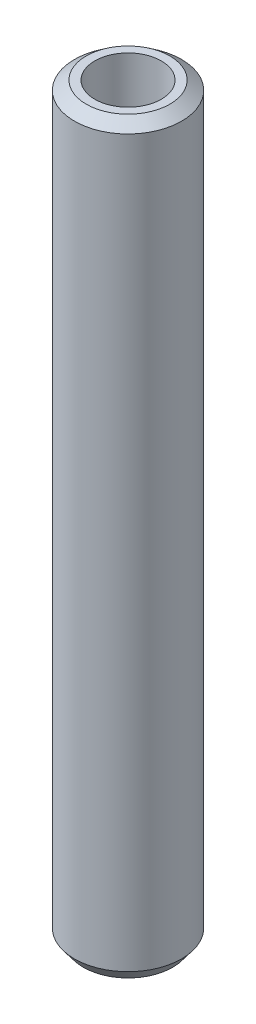
SolidWorks part; units mm, degrees
ref_plane "Front Plane" through (0, 0, 0) normal (0, 0, 1) x (1, 0, 0)
ref_plane "Top Plane" through (0, 0, 0) normal (0, 1, 0) x (1, 0, 0)
ref_plane "Right Plane" through (0, 0, 0) normal (1, 0, 0) x (0, 0, -1)
sketch "Sketch1" plane through (0, 0, 0) normal (0, 1, 0) x (1, 0, 0)
  circle A0 centre (0, 0) radius 22.5
  dimension "SHAFT_OD" = 45
extrude "Boss-Extrude1" add sketch "Sketch1" along normal blind 313.5208
sketch "Sketch2" plane through (0, 0, 0) normal (0, 1, 0) x (1, 0, 0)
  circle A0 centre (0, 0) radius 13.9804
  dimension "BORE_D" = 27.9608
extrude "Cut-Extrude1" cut sketch "Sketch2" along normal through all
chamfer "Chamfer1" distance 3.7244 angle 52.959 2 edges at (0, 313.5208, 22.5) (0, 0, 22.5) first distance on face at (0, 313.5208, 22.5) first distance on face at (0, 0, 13.9804)
